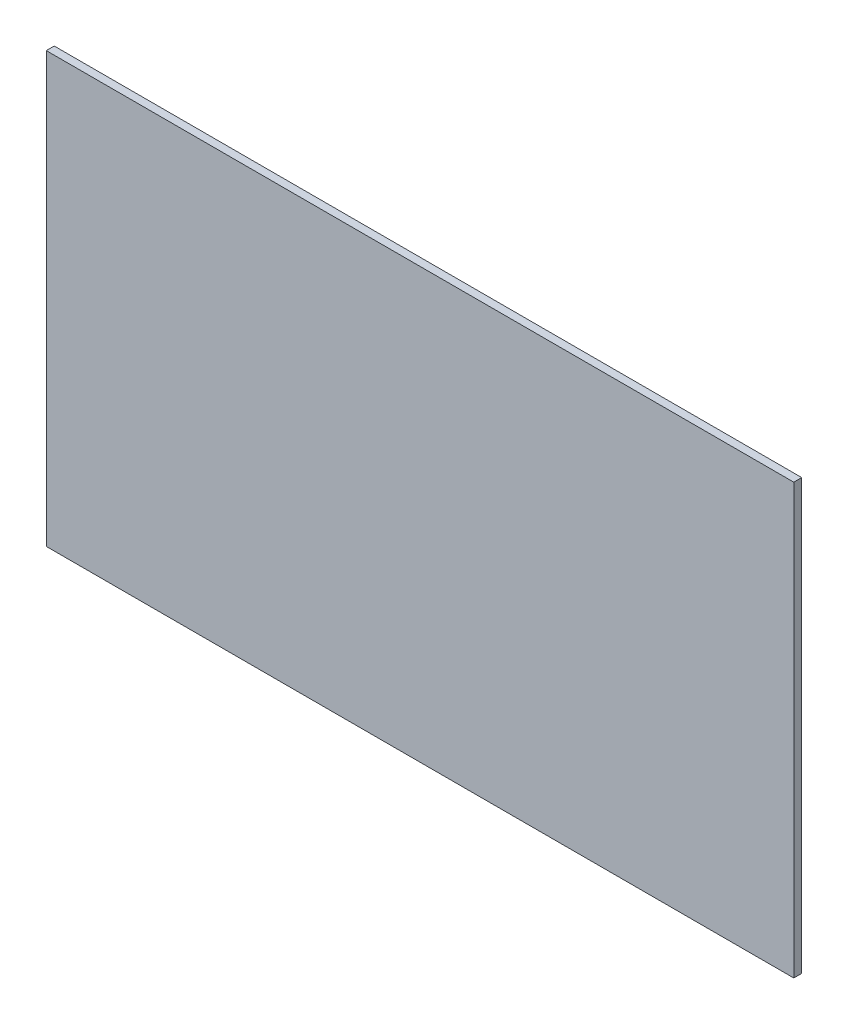
SolidWorks part; units mm, degrees
ref_plane "Front Plane" through (0, 0, 0) normal (0, 0, 1) x (1, 0, 0)
ref_plane "Top Plane" through (0, 0, 0) normal (0, 1, 0) x (1, 0, 0)
ref_plane "Right Plane" through (0, 0, 0) normal (1, 0, 0) x (0, 0, -1)
sketch "Sketch1" plane through (0, 0, 0) normal (0, 0, 1) x (1, 0, 0)
  line L1 (-149.225, -85.725) -> (149.225, -85.725)
  line L2 (-149.225, -85.725) -> (-149.225, 85.725)
  line L3 (-149.225, 85.725) -> (149.225, 85.725)
  line L4 (149.225, -85.725) -> (149.225, 85.725)
  line L5 (-149.225, -85.725) -> (149.225, 85.725) construction
  line L6 (-149.225, 85.725) -> (149.225, -85.725) construction
  point P0 (0, 0)
  dimension "D1" = 298.45
  dimension "D2" = 171.45
extrude "Boss-Extrude1" add sketch "Sketch1" along normal blind 3.175
